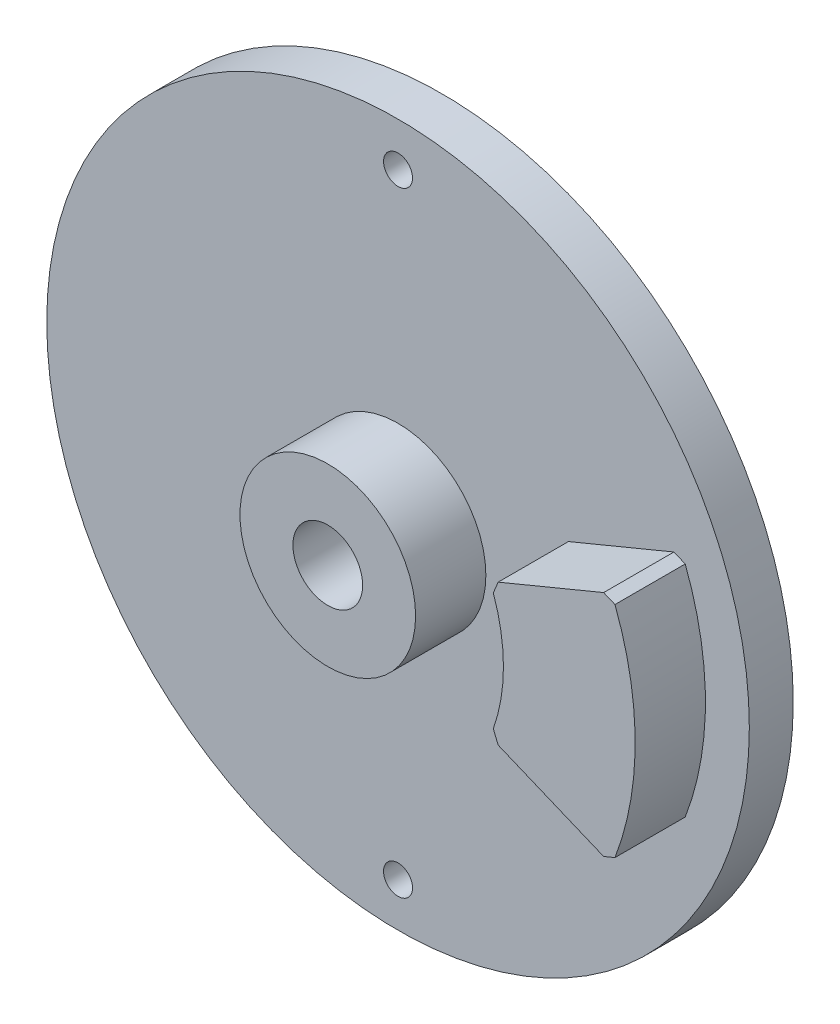
SolidWorks part; units mm, degrees
ref_plane "정면" through (0, 0, 0) normal (0, 0, 1) x (1, 0, 0)
ref_plane "윗면" through (0, 0, 0) normal (0, 1, 0) x (1, 0, 0)
ref_plane "우측면" through (0, 0, 0) normal (1, 0, 0) x (0, 0, -1)
sketch "스케치1" plane through (0, 0, 0) normal (0, 0, 1) x (1, 0, 0)
  line L1 (-40, 40) -> (40, 40)
  line L2 (-40, 40) -> (-40, -40)
  line L3 (-40, -40) -> (40, -40)
  line L4 (40, 40) -> (40, -40)
  line L5 (-40, 40) -> (40, -40) construction
  line L6 (-40, -40) -> (40, 40) construction
  circle A0 centre (0, 0) radius 40
  point P0 (0, 0)
  dimension "D1" = 80
  dimension "D2" = 80
extrude "보스-돌출1" add sketch "스케치1" along normal blind 5 contours A0 region at (0, 0, 0)
hole_wizard "M4 나사 구멍1" positions "스케치2" profile "스케치3" tap size "M4" standard "ISO" end condition up to next
sketch "스케치2" plane through (0, 0, 5) normal (0, 0, 1) x (1, 0, 0)
  line L0 (0, 35) -> (0, -35)
  circle A0 centre (0, 0) radius 40 construction
  circle A1 centre (0, 0) radius 40
  point P0 (0, -35)
  point P2 (0, 35)
  point P18 (0, 35)
  point P22 (0, 35)
  point P23 (0, 0)
  point P24 (0, 0)
  point P25 (0, 0)
  point P26 (0, 36.6243)
  point P27 (0, 0)
  point P28 (0, 35)
  point P29 (0, 0)
  dimension "D1" = 70
sketch "스케치3" plane through (0, -35, 5) normal (1, 0, 0) x (0, -1, 0)
  line L0 (0, 0) -> (0, 5)
  line L1 (0, 5) -> (1.65, 5)
  line L2 (1.65, 5) -> (1.65, 0)
  line L5 (1.65, 0) -> (0, 0)
  line L11 (0, -6.35) -> (0, 107.95) construction
  dimension "관통 탭 드릴 지름" = 3.3
  dimension "관통 탭 드릴 깊이" = 5
cosmetic thread "구멍 나사산1"
cosmetic thread "구멍 나사산2"
sketch "스케치4" plane through (0, 0, 5) normal (0, 0, 1) x (1, 0, 0)
  line L1 (35, 6.6806) -> (35, -6.6806)
  line L3 (32.3358, 13.3939) -> (18.4776, 7.6537)
  line L4 (32.3358, -13.3939) -> (18.4776, -7.6537)
  circle A0 centre (0, 0) radius 10
  arc A1 (32.3358, 13.3939) -> (32.3358, -13.3939) centre (0, 0) cw
  arc A2 (18.4776, 7.6537) -> (18.4776, -7.6537) centre (0, 0) cw
  circle A3 centre (0, 0) radius 40 construction
  point P7 (35, 0)
  point P8 (35, 0)
  dimension "D1" = 20
  dimension "D2" = 15
  dimension "D4" = 35
  dimension "D3" = 45
  dimension "D5" = 45
extrude "보스-돌출2" add sketch "스케치4" along normal blind 8 contours A0 | L3 A2 L4 A1 region at (27.4631, 0, 5) region at (0, 0, 5)
hole_wizard "3/8-16 나사 구멍1" positions "스케치7" profile "스케치8" tap size "3/8-16" standard "Ansi Inch" end condition up to next
sketch "스케치7" plane through (0, 0, 0) normal (0, 0, -1) x (-1, 0, 0)
  point P0 (0, 0)
sketch "스케치8" plane through (0, 0, 0) normal (1, 0, 0) x (0, 1, 0)
  line L0 (0, 0) -> (0, 13)
  line L1 (0, 13) -> (3.9687, 13)
  line L2 (3.9687, 13) -> (3.9687, 0)
  line L5 (3.9687, 0) -> (0, 0)
  line L11 (0, -6.35) -> (0, 107.95) construction
  dimension "관통 탭 드릴 지름" = 7.9375
  dimension "관통 탭 드릴 깊이" = 13
cosmetic thread "구멍 나사산4"
chamfer "모따기1" distance 1 angle 45 4 edges at (32.3358, -13.3939, 9) (18.4776, -7.6537, 9) (18.4776, 7.6537, 9) (32.3358, 13.3939, 9)
equation "\"D5@스케치4\"=\"D3@스케치4\""
